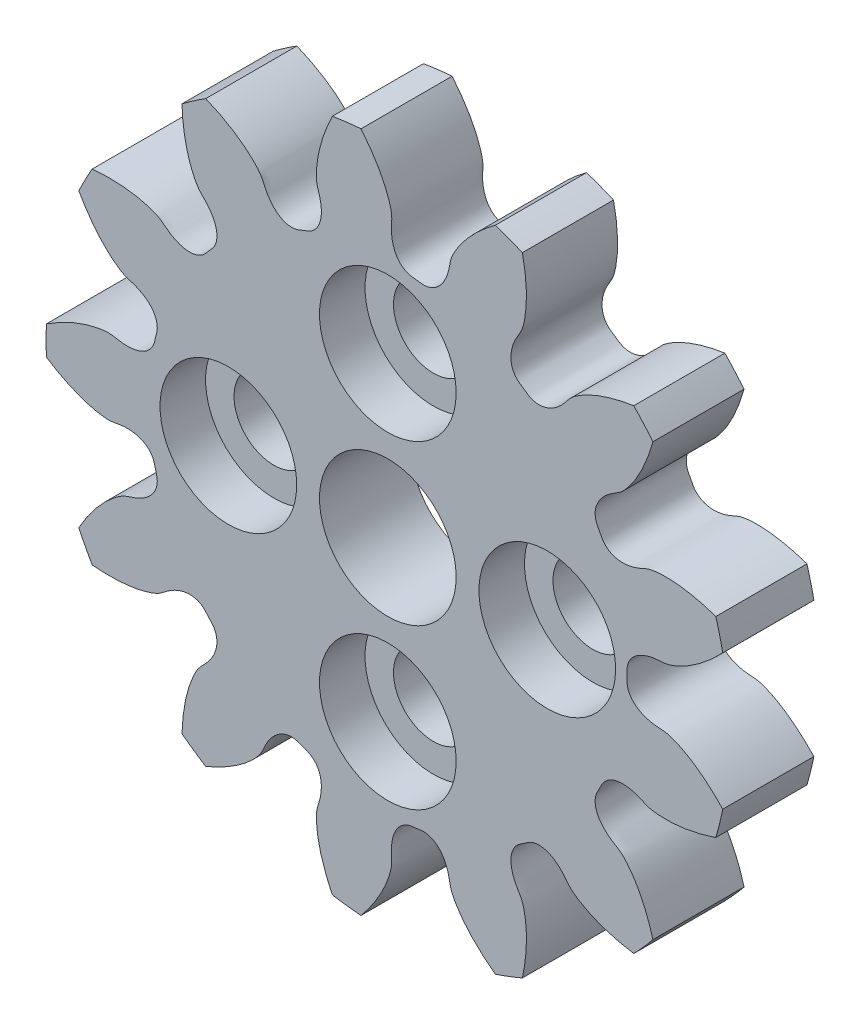
SolidWorks part; units mm, degrees
ref_plane "Front Plane" through (0, 0, 0) normal (0, 0, 1) x (1, 0, 0)
ref_plane "Top Plane" through (0, 0, 0) normal (0, 1, 0) x (1, 0, 0)
ref_plane "Right Plane" through (0, 0, 0) normal (1, 0, 0) x (0, 0, -1)
ref_axis "Axis1" through (0, 0, 55) along (0, 0, -1)
sketch "SketchRevolveSpurGear1" plane through (0, 0, 0) normal (1, 0, 0) x (0, 0, -1)
  line L0 (0, 0) -> (1, 0) construction
  line L1 (-2, 0) -> (-2, 15)
  line L2 (-2, 15) -> (2, 15)
  line L3 (2, 15) -> (2, 0)
  line L4 (2, 0) -> (-2, 0)
  dimension "Side1" = 2
  dimension "OutsideRadius" = 15
  dimension "Side2" = 2
revolve "SpurGear1" add sketch "SketchRevolveSpurGear1" angle 360 about L0
sketch "SketchToothSpurGear1" plane through (0, 0, 0) normal (0, 0, 1) x (1, 0, 0)
  arc A0 (14.7864, 3.0614) -> (14.7864, -3.0614) centre (0, 0) cw
  spline S0 degree 3 poles (14.7864, -3.0614) (14.649, -2.9104) (14.4406, -2.6967) (14.1554, -2.4351) (13.9529, -2.2625) (13.757, -2.1074) (13.5685, -1.969) (13.3885, -1.8466) (13.2178, -1.7394) (13.0573, -1.6466) (12.9077, -1.5672) (12.7699, -1.5002) (12.6445, -1.4449) (12.5322, -1.4) (12.4335, -1.365) (12.1501, -1.2718) (11.8457, -1.295) (11.554, -1.2371) (11.4615, -1.2155) (11.3719, -1.1901) (11.2852, -1.1612) (11.2012, -1.1284) (11.12, -1.0915) (11.0414, -1.0503) (10.9656, -1.0042) (10.8925, -0.9527) (10.8225, -0.8952) (10.7559, -0.831) (10.6936, -0.7591) (10.6366, -0.6789) (10.5866, -0.5899) (10.5456, -0.4922) (10.5157, -0.3867) (10.5016, -0.2863) (10.4958, -0.1568) (10.503, 0) (10.4958, 0.1568) (10.5016, 0.2863) (10.5157, 0.3867) (10.5456, 0.4922) (10.5866, 0.5899) (10.6366, 0.6789) (10.6936, 0.7591) (10.7559, 0.831) (10.8225, 0.8952) (10.8925, 0.9527) (10.9656, 1.0042) (11.0414, 1.0503) (11.12, 1.0915) (11.2012, 1.1284) (11.2852, 1.1612) (11.3719, 1.1901) (11.4615, 1.2155) (11.554, 1.2371) (11.8457, 1.295) (12.1501, 1.2718) (12.4335, 1.365) (12.5322, 1.4) (12.6445, 1.4449) (12.7699, 1.5002) (12.9077, 1.5672) (13.0573, 1.6466) (13.2178, 1.7394) (13.3885, 1.8466) (13.5685, 1.969) (13.757, 2.1074) (13.9529, 2.2625) (14.1554, 2.4351) (14.4406, 2.6967) (14.649, 2.9104) (14.7864, 3.0614) knots 0 0 0 0 0.054456 0.079535 0.10318 0.125393 0.146172 0.165518 0.183432 0.199912 0.214959 0.228573 0.240754 0.251502 0.260817 0.268698 0.330902 0.339534 0.347971 0.356236 0.364354 0.372352 0.380265 0.388132 0.395998 0.403915 0.41194 0.420135 0.428562 0.437278 0.446328 0.45573 0.465465 0.475472 0.482715 0.5 0.517285 0.524528 0.534535 0.54427 0.553672 0.562722 0.571438 0.579865 0.58806 0.596085 0.604002 0.611868 0.619735 0.627648 0.635646 0.643764 0.652029 0.660466 0.669098 0.731302 0.739183 0.748498 0.759246 0.771427 0.785041 0.800088 0.816568 0.834482 0.853828 0.874607 0.89682 0.920465 0.945544 1 1 1 1
extrude "ToothExtrudeCutSpurGear1" cut sketch "SketchToothSpurGear1" against normal blind 2 and the other way blind 2
pattern_circular "PatternSpurGear1" count 13 every 27.692 about axis through (0, 0, 55) along (0, 0, -1) of "ToothExtrudeCutSpurGear1"
sketch "BoreRevolveSketch" plane through (0, 0, 0) normal (1, 0, 0) x (0, 0, -1)
  line L0 (0, 0) -> (1, 0) construction
  line L1 (-2, 0) -> (2, 0)
  line L2 (2, 0) -> (2, 3)
  line L3 (2, 3) -> (-2, 3)
  line L4 (-2, 3) -> (-2, 0)
  dimension "BoreSide1" = 2
  dimension "BoreSide2" = 2
  dimension "TaperSide2" = 3
revolve "BoreRevolveCut" cut sketch "BoreRevolveSketch" angle 360 about L0
sketch "AuxiliarySketchSpurGear1" plane through (0, 0, 0) normal (0, 0, 1) x (1, 0, 0)
  circle A0 centre (0, 0) radius 13 construction
  circle A1 centre (0, 0) radius 12.216 construction
  circle A2 centre (0, 0) radius 12.335 construction
  circle A3 centre (0, 0) radius 15 construction
  circle A4 centre (0, 0) radius 10.5 construction
  dimension "PitchDiameter" = 26
  dimension "BaseDiameter" = 24.432
  dimension "FormDiameter" = 24.6699
  dimension "MajorDiameter" = 30
  dimension "MinorDiameter" = 21
sketch "Sketch1" plane through (0, 0, 2) normal (0, 0, 1) x (1, 0, 0)
  circle A0 centre (0, 0) radius 7 construction
  circle A1 centre (0, 7) radius 1.75
  circle A3 centre (7, 0) radius 1.75
  circle A4 centre (0, -7) radius 1.75
  circle A5 centre (-7, 0) radius 1.75
  point P14 (0, 0)
  dimension "D1" = 14
  dimension "D2" = 3.5
  dimension "D3" = 4
extrude "Cut-Extrude1" cut sketch "Sketch1" against normal through all
sketch "Sketch2" plane through (0, 0, 2) normal (0, 0, 1) x (1, 0, 0)
  circle A0 centre (0, 7) radius 3
  circle A1 centre (7, 0) radius 3
  circle A2 centre (0, -7) radius 3
  circle A3 centre (-7, 0) radius 3
  dimension "D1" = 6
extrude "Cut-Extrude2" cut sketch "Sketch2" against normal blind 2
